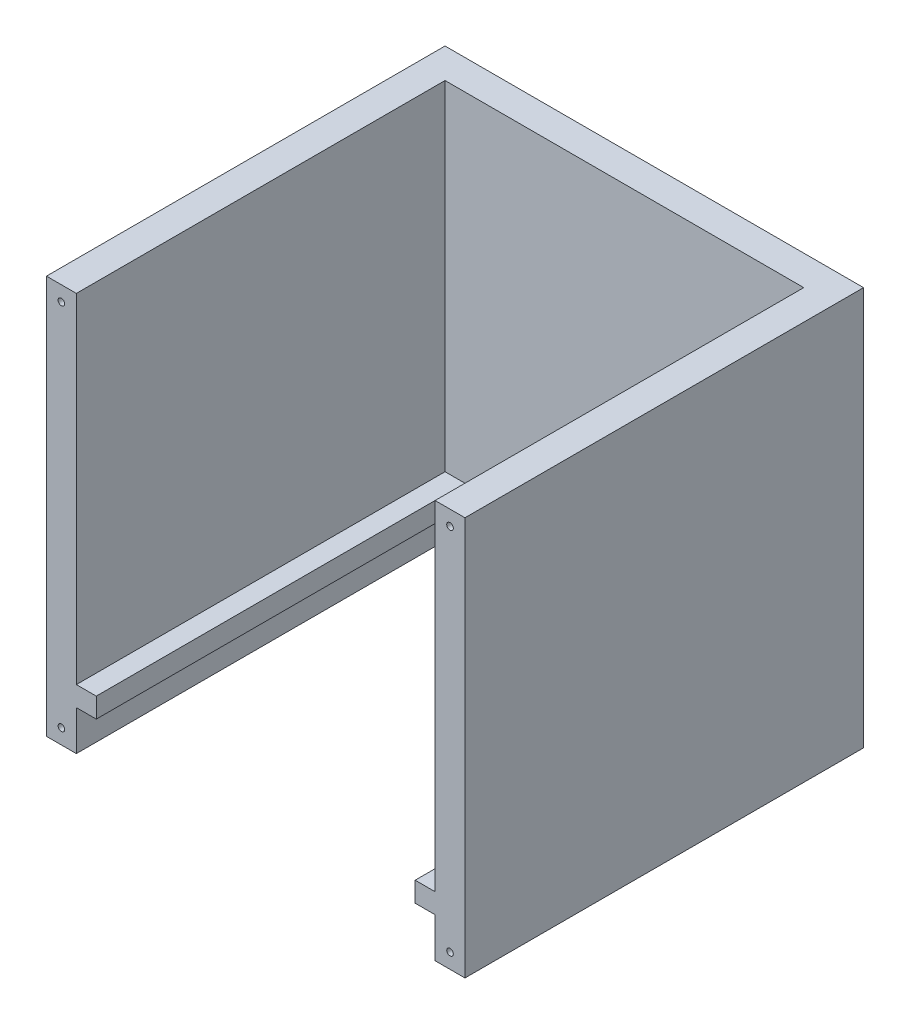
SolidWorks part; units mm, degrees
ref_plane "Front Plane" through (0, 0, 0) normal (0, 0, 1) x (1, 0, 0)
ref_plane "Top Plane" through (0, 0, 0) normal (0, 1, 0) x (1, 0, 0)
ref_plane "Right Plane" through (0, 0, 0) normal (1, 0, 0) x (0, 0, -1)
sketch "Sketch2" plane through (0, 0, 0) normal (0, 1, 0) x (1, 0, 0)
  line L0 (-90, 0) -> (90, 0)
  line L1 (90, 0) -> (90, -185)
  line L2 (-90, 0) -> (-90, -185)
  line L3 (-90, -185) -> (-105, -185)
  line L4 (-105, -185) -> (-105, 15)
  line L5 (-105, 15) -> (105, 15)
  line L6 (105, 15) -> (105, -185)
  line L7 (105, -185) -> (90, -185)
  dimension "D1" = 180
  dimension "D2" = 185
  dimension "D3" = 15
  dimension "D4" = 15
extrude "Boss-Extrude1" add sketch "Sketch2" along normal blind 200
ref_plane "Plane1" through (0, 30, 0) normal (0, 1, 0) x (1, 0, 0)
sketch "Sketch3" plane through (0, 30, 0) normal (0, 1, 0) x (1, 0, 0)
  line L0 (-90, -185) -> (-80, -185)
  line L1 (-80, -185) -> (-80, -10)
  line L2 (-80, -10) -> (80, -10)
  line L3 (80, -10) -> (80, -185)
  line L4 (80, -185) -> (90, -185)
  line L5 (-90, 0) -> (90, 0) construction
  line L14 (-90, -185) -> (-90, 0)
  line L15 (-90, 0) -> (90, 0)
  line L16 (90, 0) -> (90, -185)
  line L17 (90, -185) -> (105, -185)
  line L18 (105, -185) -> (105, 15)
  line L19 (105, 15) -> (-105, 15)
  line L20 (-105, 15) -> (-105, -185)
  line L21 (-105, -185) -> (-90, -185)
  line L22 (-90, -185) -> (-90, 0)
  line L23 (-90, 0) -> (90, 0)
  line L24 (90, 0) -> (90, -185)
  dimension "D1" = 10
  dimension "D2" = 10
  dimension "D3" = 0
extrude "Boss-Extrude2" add sketch "Sketch3" against normal blind 10
sketch "Sketch5" plane through (0, 0, 185) normal (0, 0, 1) x (1, 0, 0)
  line L0 (-105, 200) -> (-90, 200) construction
  line L1 (-105, 200) -> (-105, 0) construction
  line L2 (0, 0) -> (0, 50000) construction
  line L3 (-105, 0) -> (-90, 0) construction
  circle A0 centre (-97.5, 192.5) radius 1.65
  circle A1 centre (97.5, 192.5) radius 1.65
  circle A2 centre (-97.5, 7.5) radius 1.65
  circle A3 centre (97.5, 7.5) radius 1.65
  point P4 (-97.5, 200)
  dimension "D1" = 3.3
  dimension "D4" = 3.3
  dimension "D2" = 7.5
  dimension "D3" = 7.5
  dimension "D5" = 7.5
  dimension "D6" = 7.5
extrude "Cut-Extrude1" cut sketch "Sketch5" against normal blind 10 contours A2 | A1 | A0 | A3
